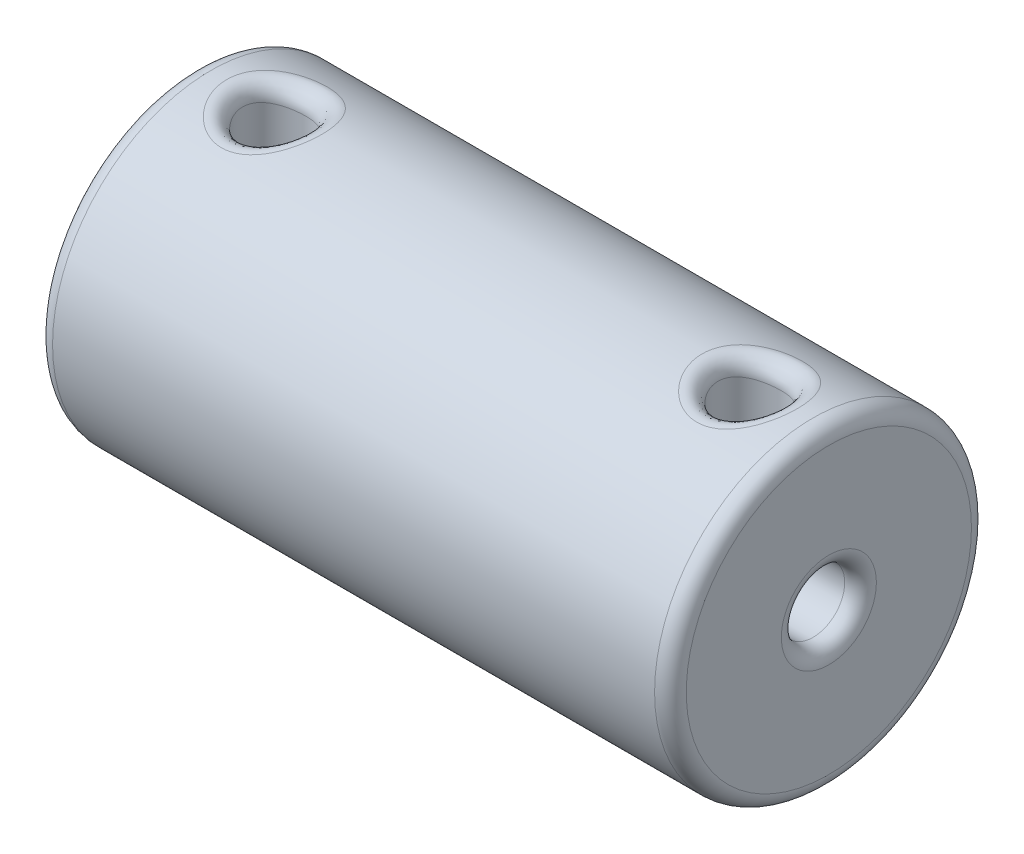
SolidWorks part; units mm, degrees
ref_plane "Front Plane" through (0, 0, 0) normal (0, 0, 1) x (1, 0, 0)
ref_plane "Top Plane" through (0, 0, 0) normal (0, 1, 0) x (1, 0, 0)
ref_plane "Right Plane" through (0, 0, 0) normal (1, 0, 0) x (0, 0, -1)
sketch "Sketch1" plane through (0, 0, 0) normal (1, 0, 0) x (0, 0, -1)
  circle A0 centre (0, 0) radius 5
  dimension "D1" = 10
extrude "Boss-Extrude1" add sketch "Sketch1" along normal blind 10 and the other way blind 10
sketch "Sketch2" plane through (10, 0, 0) normal (1, 0, 0) x (0, 0, -1)
  circle A0 centre (0, 0) radius 1
  dimension "D1" = 2
extrude "Cut-Extrude1" cut sketch "Sketch2" against normal blind 10
sketch "Sketch3" plane through (-10, 0, 0) normal (-1, 0, 0) x (0, 0, 1)
  circle A0 centre (0, 0) radius 2
  dimension "D1" = 4
extrude "Cut-Extrude2" cut sketch "Sketch3" against normal blind 10
sketch "Sketch4" plane through (0, 0, 0) normal (0, 1, 0) x (1, 0, 0)
  line L0 (-10, 0) -> (10, 0) construction
  line L1 (-10, 5) -> (-10, -5) construction
  line L2 (10, -5) -> (10, 5) construction
  circle A0 centre (-7.5, 0) radius 1
  circle A1 centre (7.5, 0) radius 1
  dimension "D3" = 2
  dimension "D4" = 2
  dimension "D1" = 2.5
  dimension "D2" = 2.5
extrude "Cut-Extrude4" cut sketch "Sketch4" along normal up to next
fillet "Fillet1" radius 0.5 4 edges at (10, 0, -1) (10, 0, -5) (-10, 0, -5) (-10, 0, 2)
fillet "Fillet2" radius 0.5 2 edges at (7.7079, 4.9034, 0.9782) (-7.2921, 4.9034, 0.9782)
